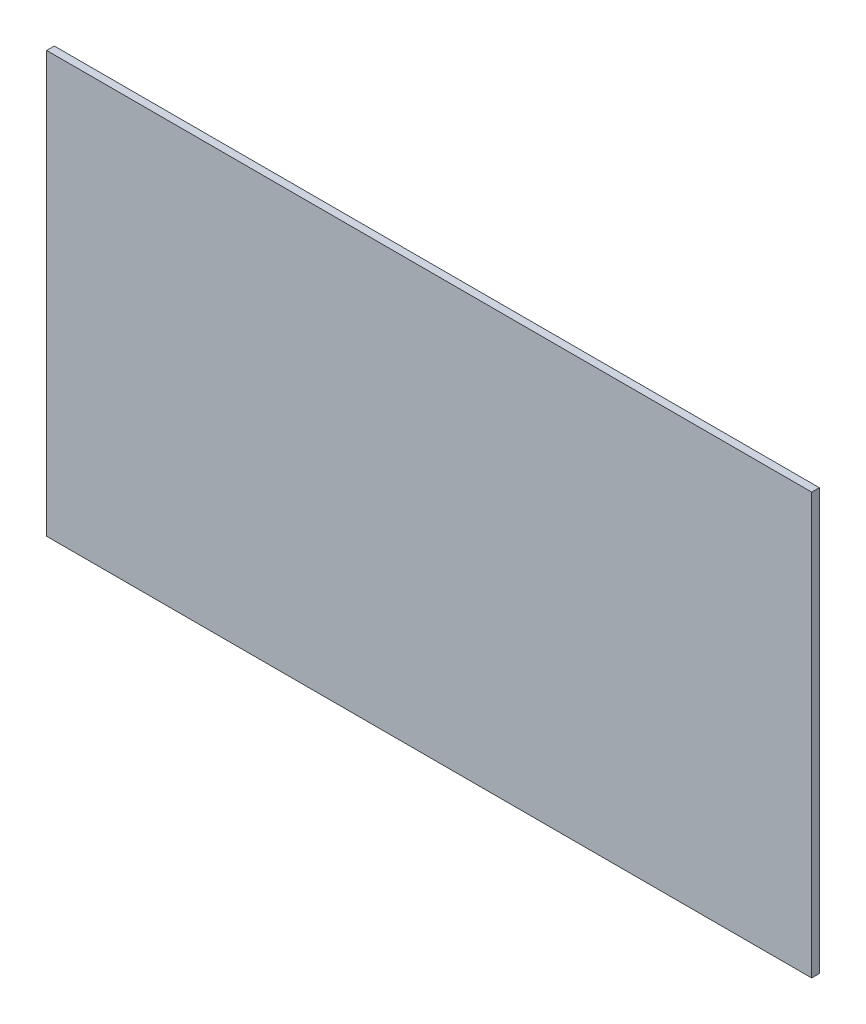
SolidWorks part; units mm, degrees
ref_plane "Front Plane" through (0, 0, 0) normal (0, 0, 1) x (1, 0, 0)
ref_plane "Top Plane" through (0, 0, 0) normal (0, 1, 0) x (1, 0, 0)
ref_plane "Right Plane" through (0, 0, 0) normal (1, 0, 0) x (0, 0, -1)
sketch "Sketch1" plane through (0, 0, 0) normal (0, 0, 1) x (1, 0, 0)
  line L1 (-200, 110) -> (200, 110)
  line L2 (-200, 110) -> (-200, -110)
  line L3 (-200, -110) -> (200, -110)
  line L4 (200, 110) -> (200, -110)
  dimension "D1" = 400
  dimension "D2" = 220
  dimension "D3" = 110
  dimension "D4" = 200
extrude "Boss-Extrude1" add sketch "Sketch1" along normal blind 4
